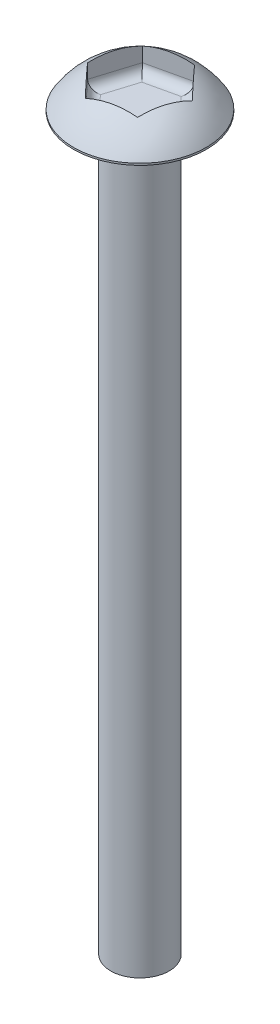
SolidWorks part; units mm, degrees
ref_plane "Front Plane" through (0, 0, 0) normal (0, 0, 1) x (1, 0, 0)
ref_plane "Top Plane" through (0, 0, 0) normal (0, 1, 0) x (1, 0, 0)
ref_plane "Right Plane" through (0, 0, 0) normal (1, 0, 0) x (0, 0, -1)
sketch "Sketch1" plane through (0, 0, 0) normal (0, 1, 0) x (1, 0, 0)
  circle A0 centre (0, 0) radius 4
  dimension "D1" = 8
extrude "Boss-Extrude1" add sketch "Sketch1" along normal blind 100
sketch "Sketch2" plane through (0, 100, 0) normal (0, 1, 0) x (1, 0, 0)
  circle A0 centre (0, 0) radius 9.0966
extrude "Boss-Extrude2" add sketch "Sketch2" along normal blind 0.254
sketch "Sketch3" plane through (0, 100.254, 0) normal (0, 1, 0) x (1, 0, 0)
  line L1 (1.771, 5.7205) -> (-4.0686, 4.3939)
  line L2 (-4.0686, 4.3939) -> (-5.8396, -1.3265)
  line L3 (-5.8396, -1.3265) -> (-1.771, -5.7205)
  line L4 (-1.771, -5.7205) -> (4.0686, -4.3939)
  line L5 (4.0686, -4.3939) -> (5.8396, 1.3265)
  line L6 (5.8396, 1.3265) -> (1.771, 5.7205)
  circle A0 centre (0, 0) radius 5.1861 construction
dome "Dome1" faces to dome 1 distance 5.08 reverse direction no elliptical dome no face at (0, 100.254, 9.0966) parameters "D1"=5.08
extrude "Cut-Extrude1" cut sketch "Sketch3" along normal through all contours L3 L4 L5 L6 L1 L2
fillet "Fillet1" radius 1.27 6 edges at (-1.1488, 100.254, -5.0572) (3.8053, 100.254, -3.5235) (4.9541, 100.254, 1.5337) (1.1488, 100.254, 5.0572) (-3.8053, 100.254, 3.5235) (-4.9541, 100.254, -1.5337)
